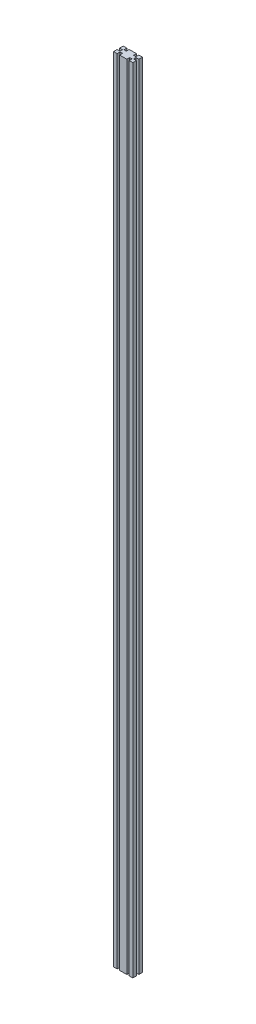
SolidWorks part; units mm, degrees
ref_plane "Front Plane" through (0, 0, 0) normal (0, 0, 1) x (1, 0, 0)
ref_plane "Top Plane" through (0, 0, 0) normal (0, 1, 0) x (1, 0, 0)
ref_plane "Right Plane" through (0, 0, 0) normal (1, 0, 0) x (0, 0, -1)
sketch "Sketch1" plane through (0, 0, 0) normal (0, 1, 0) x (1, 0, 0)
  line L1 (-20, -10) -> (20, -10)
  line L2 (-20, -10) -> (-20, 10)
  line L3 (-20, 10) -> (20, 10)
  line L4 (20, -10) -> (20, 10)
  line L5 (-20, -10) -> (20, 10) construction
  line L6 (-20, 10) -> (20, -10) construction
  point P0 (0, 0)
  dimension "D1" = 20
  dimension "D2" = 40
extrude "Boss-Extrude1" add sketch "Sketch1" along normal blind 825.5 and the other way blind 825.5
sketch "Sketch2" plane through (0, 0, 0) normal (0, 1, 0) x (1, 0, 0)
  line L0 (-20, 10) -> (0, 10) construction
  line L1 (20, 10) -> (-20, 10) construction
  line L2 (0, 10) -> (20, 10) construction
  line L4 (-20, 10) -> (-20, -10) construction
  line L5 (-12.5, 4) -> (-7.5, 4)
  line L6 (-12.5, 4) -> (-12.5, 16)
  line L7 (-12.5, 16) -> (-7.5, 16)
  line L8 (-7.5, 4) -> (-7.5, 16)
  line L9 (-12.5, 4) -> (-7.5, 16) construction
  line L10 (-12.5, 16) -> (-7.5, 4) construction
  line L11 (-14, 2.5) -> (-26, 2.5)
  line L12 (-14, 2.5) -> (-14, -2.5)
  line L13 (-14, -2.5) -> (-26, -2.5)
  line L14 (-26, 2.5) -> (-26, -2.5)
  line L15 (-14, 2.5) -> (-26, -2.5) construction
  line L16 (-14, -2.5) -> (-26, 2.5) construction
  line L17 (-55, 0) -> (55, 0) construction
  line L18 (-14, 2.5) -> (-26, -2.5) construction
  line L19 (-14, -2.5) -> (-26, 2.5) construction
  line L20 (-12.5, -16) -> (-7.5, -4) construction
  line L21 (-12.5, -4) -> (-7.5, -16) construction
  line L22 (-14, 2.5) -> (-26, 2.5)
  line L23 (-14, -2.5) -> (-26, -2.5)
  line L24 (-7.5, -4) -> (-7.5, -16)
  line L25 (-12.5, -16) -> (-7.5, -16)
  line L26 (-12.5, -4) -> (-12.5, -16)
  line L27 (-12.5, -4) -> (-7.5, -4)
  line L28 (0, -55) -> (0, 55) construction
  line L29 (12.5, -4) -> (7.5, -16) construction
  line L30 (12.5, -16) -> (7.5, -4) construction
  line L31 (14, -2.5) -> (26, 2.5) construction
  line L32 (14, 2.5) -> (26, -2.5) construction
  line L33 (14, -2.5) -> (26, 2.5) construction
  line L34 (14, 2.5) -> (26, -2.5) construction
  line L35 (12.5, 16) -> (7.5, 4) construction
  line L36 (12.5, 4) -> (7.5, 16) construction
  line L37 (20, 10) -> (0, 10) construction
  line L38 (12.5, -4) -> (7.5, -4)
  line L39 (12.5, -4) -> (12.5, -16)
  line L40 (12.5, -16) -> (7.5, -16)
  line L41 (7.5, -4) -> (7.5, -16)
  line L42 (14, -2.5) -> (26, -2.5)
  line L43 (14, 2.5) -> (26, 2.5)
  line L44 (26, 2.5) -> (26, -2.5)
  line L45 (14, -2.5) -> (26, -2.5)
  line L46 (14, 2.5) -> (14, -2.5)
  line L47 (14, 2.5) -> (26, 2.5)
  line L48 (7.5, 4) -> (7.5, 16)
  line L49 (12.5, 16) -> (7.5, 16)
  line L50 (12.5, 4) -> (12.5, 16)
  line L51 (12.5, 4) -> (7.5, 4)
  point P7 (-10, 10)
  point P12 (-20, 0)
  point P25 (-10, -10)
  point P40 (10, -10)
  point P41 (20, 0)
  point P42 (10, 10)
  dimension "D1" = 12
  dimension "D2" = 5
  dimension "D3" = 5
  dimension "D4" = 12
extrude "Cut-Extrude1" cut sketch "Sketch2" against normal through all both and the other way through all contours L5 L8 L7 L6 | L27 L26 L25 L24 | L11 L14 L13 L12 | L51 L50 L49 L48 | L43 L46 L42 L44 | L38 L41 L40 L39 region at (-10, 0, -10) region at (-20, 0, 0) region at (-10, 0, 10) region at (10, 0, 10) region at (20, 0, 0) region at (10, 0, -10)
